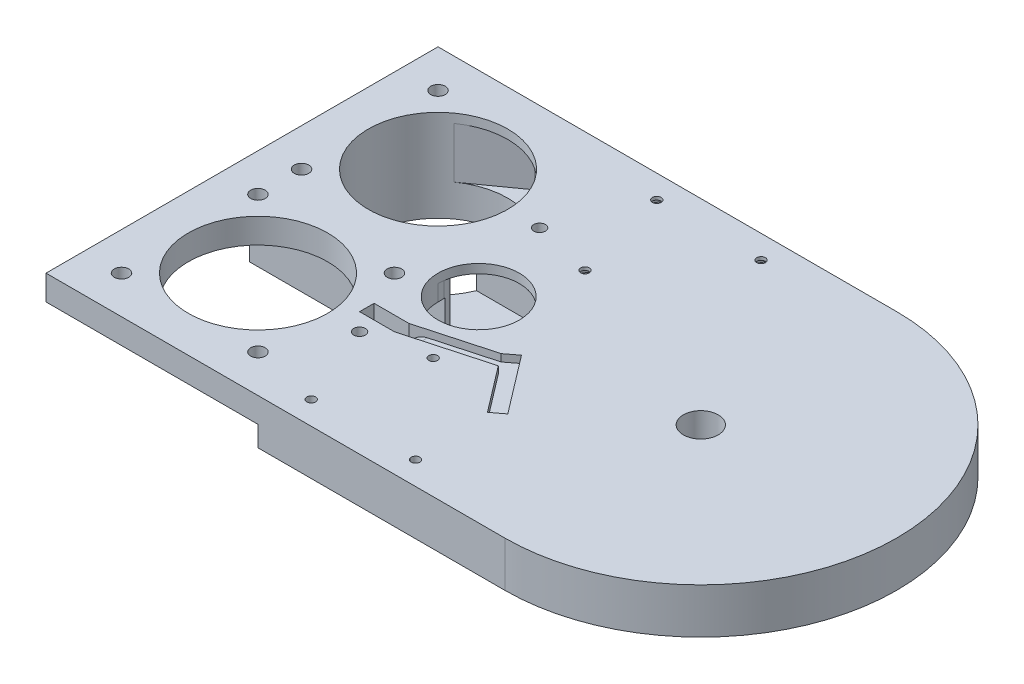
SolidWorks part; units mm, degrees
ref_plane "Alzado" through (0, 0, 0) normal (0, 0, 1) x (1, 0, 0)
ref_plane "Planta" through (0, 0, 0) normal (0, 1, 0) x (1, 0, 0)
ref_plane "Vista lateral" through (0, 0, 0) normal (1, 0, 0) x (0, 0, -1)
sketch "Croquis1" plane through (0, 0, 0) normal (0, 1, 0) x (1, 0, 0)
  line L1 (0, -67.5) -> (-158, -67.5)
  line L3 (0, 67.5) -> (-158, 67.5)
  line L4 (-158, -67.5) -> (-158, 67.5)
  arc A0 (0, -67.5) -> (0, 67.5) centre (0, 0) ccw
  dimension "D2" = 135
  dimension "D1" = 158
extrude "Saliente-Extruir4" add sketch "Croquis1" along normal blind 8.6
sketch "Croquis3" plane through (0, 0, 0) normal (0, -1, 0) x (1, 0, 0)
  line L0 (-85, -67.5) -> (-68.1481, -2.5)
  line L1 (-71.4961, -15.4136) -> (-68.1506, -2.5096) construction
  line L3 (-68.1481, -2.5) -> (-158, -2.5)
  line L4 (-158, -2.5) -> (-158, -67.5)
  line L5 (-158, -67.5) -> (-85, -67.5)
extrude "Saliente-Extruir2" add sketch "Croquis3" along normal up to surface (23 mm away)
sketch "Croquis2" plane through (0, 0, 0) normal (0, 1, 0) x (1, 0, 0)
  line L0 (-17.38, 0) -> (17.38, 0) construction
  circle A0 centre (-76.5, 0) radius 14
  circle A2 centre (-121.5, 31) radius 24
  circle A3 centre (-121.5, -31) radius 24
  dimension "D1" = 28
  dimension "D2" = 48
extrude "Cortar-Extruir1" cut sketch "Croquis2" along normal through all both and the other way through all
sketch "Croquis5" plane through (0, 8.6, 0) normal (0, 1, 0) x (1, 0, 0)
  circle A0 centre (-145, -7.5) radius 2.5
  circle A1 centre (-145, -54.5) radius 2.5
  circle A2 centre (-98, -54.5) radius 2.5
  circle A3 centre (-98, -7.5) radius 2.5
  circle A4 centre (-145, 7.5) radius 2.5
  circle A5 centre (-145, 54.5) radius 2.5
  dimension "D1" = 5
extrude "Cortar-Extruir2" cut sketch "Croquis5" against normal through all
sketch "Croquis6" plane through (0, 8.6, 0) normal (0, 1, 0) x (1, 0, 0)
  line L0 (0, -67.5) -> (-85, -67.5)
  line L1 (-85, -67.5) -> (-70.8172, -12.7947)
  line L2 (0, 67.5) -> (-85, 67.5)
  line L3 (-85, 67.5) -> (-70.8172, 12.7947)
  line L4 (0, 67.5) -> (-158, 67.5) construction
  arc A1 (0, -67.5) -> (0, 67.5) centre (0, 0) ccw
  arc A3 (-70.8172, -12.7947) -> (-70.8172, 12.7947) centre (-76.5, 0) ccw
  circle A4 centre (-76.5, 0) radius 14 construction
  arc A5 (0, -67.5) -> (0, 67.5) centre (0, 0) ccw construction
extrude "Saliente-Extruir3" add sketch "Croquis6" against normal blind 15.6
sketch "Croquis7" plane through (0, 0, 0) normal (0, 1, 0) x (1, 0, 0)
  circle A0 centre (0, 0) radius 6
  dimension "D1" = 12
extrude "Cortar-Extruir3" cut sketch "Croquis7" against normal through all both and the other way through all
sketch "Croquis8" plane through (0, -7, 0) normal (0, -1, 0) x (1, 0, 0)
  line L0 (0, -63) -> (-116.397, -63)
  line L1 (-119.3042, -62.068) -> (-135.4544, -50.5263)
  line L2 (-158, -67.5) -> (-158, -2.5) construction
  line L3 (-121.5, -7) -> (-95.5, -7)
  line L4 (-90.5, -2) -> (-90.5, 0)
  arc A0 (0, -63) -> (-61.2515, 14.7395) centre (0, 0) ccw
  circle A1 centre (-121.5, -31) radius 24 construction
  arc A2 (-121.5, -7) -> (-135.4544, -50.5263) centre (-121.5, -31) ccw
  arc A4 (-70.8172, 12.7947) -> (-90.275, -2.5) centre (-76.5, 0) ccw construction
  arc A7 (-70.8172, 12.7947) -> (-90.5, 0) centre (-76.5, 0) ccw
  arc A10 (-70.8172, -12.7947) -> (-70.8172, 12.7947) centre (-76.5, 0) ccw construction
  arc A11 (-68.8462, 11.7226) -> (-70.8172, 12.7947) centre (-76.5, 0) ccw
  arc A12 (-61.2515, 14.7395) -> (-68.8462, 11.7226) centre (-66.1127, 15.9093) cw
  arc A13 (-90.5, -2) -> (-95.5, -7) centre (-95.5, -2) cw
  arc A14 (-116.397, -63) -> (-119.3042, -62.068) centre (-116.397, -58) cw
  point P27 (-118, -63)
  dimension "D1" = 126
  dimension "D3" = 5
  dimension "D4" = 5
  dimension "D5" = 5
  dimension "D2" = 40
extrude "Cortar-Extruir4" cut sketch "Croquis8" against normal blind 12.5 and the other way blind 5 body kept at (0, 8.6, 67.5)
fillet "Redondeo1" radius 2 1 edges at (-70.8172, -17.5, -12.7947)
sketch "Croquis9" plane through (0, 5.5, 0) normal (0, -1, 0) x (1, 0, 0)
  circle A0 centre (0, 0) radius 6 construction
  circle A1 centre (0, 0) radius 6
  circle A2 centre (0, 0) radius 16.85
  dimension "D1" = 33.7
extrude "Saliente-Extruir5" add sketch "Croquis9" along normal blind 4.65
sketch "Croquis10" plane through (0, 0.85, 0) normal (0, -1, 0) x (1, 0, 0)
  circle A0 centre (0, 0) radius 6 construction
  circle A1 centre (0, 0) radius 6
  circle A2 centre (0, 0) radius 10
  dimension "D1" = 20
extrude "Saliente-Extruir6" add sketch "Croquis10" along normal blind 29
fillet "Redondeo2" radius 0.5 1 edges at (0, 0.85, -16.85)
fillet "Redondeo3" radius 2 1 edges at (0, 5.5, -16.85)
sketch "Croquis11" plane through (0, 5.5, 0) normal (0, -1, 0) x (1, 0, 0)
  line L0 (-121.5, -31) -> (-75.537, -31) construction
  line L1 (-71.7118, -16.2457) -> (-85, -67.5) construction
  line L2 (-73.2037, -22) -> (-77.8704, -40)
  line L3 (-99.2514, -22) -> (-73.2037, -22)
  line L4 (-99.2514, -40) -> (-77.8704, -40)
  circle A0 centre (-121.5, -31) radius 24 construction
  arc A1 (-99.2514, -40) -> (-99.2514, -22) centre (-121.5, -31) ccw
  dimension "D1" = 9
extrude "Saliente-Extruir7" add sketch "Croquis11" along normal up to next
sketch "Croquis12" plane through (0, -7, 0) normal (0, -1, 0) x (1, 0, 0)
  line L2 (-63.0732, 14.8024) -> (-77.256, 69.5077)
  line L3 (-63.0732, 14.8024) -> (-77.256, 69.5077) construction
  line L4 (20.2125, 0) -> (-20.2125, 0) construction
  line L5 (-85, 59.5) -> (0, 59.5)
  line L6 (-85, 59.5) -> (0, 59.5) construction
  circle A0 centre (0, 0) radius 71 construction
  circle A2 centre (-74.6614, 59.5) radius 1.5
  circle A3 centre (-66.0127, 26.1405) radius 1.5
  circle A4 centre (-38.7395, 59.5) radius 1.5
  circle A5 centre (-38.7395, -59.5) radius 1.5
  circle A6 centre (-74.6614, -59.5) radius 1.5
  circle A7 centre (-66.0127, -26.1405) radius 1.5
  circle A8 centre (0, 0) radius 67.5 construction
  arc A9 (0, -67.5) -> (0, 67.5) centre (0, 0) ccw construction
  dimension "D1" = 142
  dimension "D4" = 3
  dimension "D2" = 8
  dimension "D3" = 8
extrude "Cortar-Extruir5" cut sketch "Croquis12" against normal through all
sketch "Croquis13" plane through (0, 5.5, 0) normal (0, -1, 0) x (1, 0, 0)
  line L1 (-70.9087, -59.5) -> (-72.785, -56.25)
  line L2 (-72.785, -56.25) -> (-76.5378, -56.25)
  line L3 (-76.5378, -56.25) -> (-78.4142, -59.5)
  line L4 (-78.4142, -59.5) -> (-76.5378, -62.75)
  line L5 (-76.5378, -62.75) -> (-72.785, -62.75)
  line L6 (-72.785, -62.75) -> (-70.9087, -59.5)
  line L7 (-62.2599, -26.1405) -> (-64.1363, -22.8905)
  line L8 (-64.1363, -22.8905) -> (-67.8891, -22.8905)
  line L9 (-67.8891, -22.8905) -> (-69.7655, -26.1405)
  line L10 (-69.7655, -26.1405) -> (-67.8891, -29.3905)
  line L11 (-67.8891, -29.3905) -> (-64.1363, -29.3905)
  line L12 (-64.1363, -29.3905) -> (-62.2599, -26.1405)
  line L13 (-34.9867, -59.5) -> (-36.8631, -56.25)
  line L14 (-36.8631, -56.25) -> (-40.6159, -56.25)
  line L15 (-40.6159, -56.25) -> (-42.4923, -59.5)
  line L16 (-42.4923, -59.5) -> (-40.6159, -62.75)
  line L17 (-40.6159, -62.75) -> (-36.8631, -62.75)
  line L18 (-36.8631, -62.75) -> (-34.9867, -59.5)
  circle A0 centre (-74.6614, -59.5) radius 3.25 construction
  circle A1 centre (-66.0127, -26.1405) radius 3.25 construction
  circle A2 centre (-38.7395, -59.5) radius 3.25 construction
  dimension "D1" = 6.5
extrude "Cortar-Extruir6" cut sketch "Croquis13" against normal blind 2
sketch "Croquis14" plane through (0, -7, 0) normal (0, -1, 0) x (1, 0, 0)
  circle A0 centre (-66.0127, 26.1405) radius 3
  circle A1 centre (-74.6614, 59.5) radius 3
  circle A2 centre (-38.7395, 59.5) radius 3
  dimension "D1" = 6
extrude "Cortar-Extruir7" cut sketch "Croquis14" against normal blind 3.7
sketch "Croquis15" plane through (0, -23, 0) normal (0, -1, 0) x (1, 0, 0)
  line L0 (-71.7118, -16.2457) -> (-85, -67.5) construction
  line L1 (-97.5, -31) -> (-75.537, -31) construction
  line L2 (20.2125, 0) -> (-20.2125, 0) construction
  circle A0 centre (-121.5, -31) radius 24 construction
  circle A1 centre (-86.5185, -31) radius 2
  circle A2 centre (-86.5185, 31) radius 2
  dimension "D1" = 4
extrude "Cortar-Extruir8" cut sketch "Croquis15" against normal through all
sketch "Croquis16" plane through (0, 0, 0) normal (0, -1, 0) x (1, 0, 0)
  circle A0 centre (-86.5185, 31) radius 4
  dimension "D1" = 8
extrude "Cortar-Extruir9" cut sketch "Croquis16" against normal blind 4
sketch "Croquis17" plane through (0, -23, 0) normal (0, -1, 0) x (1, 0, 0)
  line L1 (-82.1884, -31) -> (-84.3535, -27.25)
  line L2 (-84.3535, -27.25) -> (-88.6836, -27.25)
  line L3 (-88.6836, -27.25) -> (-90.8486, -31)
  line L4 (-90.8486, -31) -> (-88.6836, -34.75)
  line L5 (-88.6836, -34.75) -> (-84.3535, -34.75)
  line L6 (-84.3535, -34.75) -> (-82.1884, -31)
  circle A0 centre (-86.5185, -31) radius 3.75 construction
  dimension "D1" = 7.5
extrude "Cortar-Extruir10" cut sketch "Croquis17" against normal blind 10
sketch "Croquis19" plane through (0, 8.6, 0) normal (0, 1, 0) x (1, 0, 0)
  line L0 (0, -20.2125) -> (0, 20.2125) construction
  line L1 (-158, -67.5) -> (0, -67.5) construction
  line L2 (-52.483, -17.2558) -> (-40.4717, -33.0039)
  line L3 (-55.6329, -13.1259) -> (-51.6573, -10.0936)
  line L4 (-40.4717, -33.0039) -> (-36.4961, -29.9717)
  line L5 (-51.6573, -10.0936) -> (-36.4961, -29.9717)
  line L6 (-55.6329, -13.1259) -> (-36.4961, -29.9717) construction
  line L7 (-40.4717, -33.0039) -> (-51.6573, -10.0936) construction
  line L8 (-40, -29.5) -> (-62.5, 0) construction
  line L9 (-20.2125, 0) -> (20.2125, 0) construction
  line L10 (-80.5185, -20) -> (-55.6329, -13.1259)
  line L11 (-92.5185, -25) -> (-80.5185, -25)
  line L12 (-92.5185, -25) -> (-92.5185, -20)
  line L13 (-92.5185, -20) -> (-80.5185, -20)
  line L15 (-92.5185, -25) -> (-80.5185, -20) construction
  line L16 (-92.5185, -20) -> (-80.5185, -25) construction
  line L17 (-80.5185, -25) -> (-52.483, -17.2558)
  circle A0 centre (-40, -29.5) radius 2.5 construction
  circle A1 centre (-76.5, 0) radius 14 construction
  circle A2 centre (-86.5185, -31) radius 2 construction
  circle A3 centre (-86.5185, -31) radius 2 construction
  point P7 (-46.0645, -21.5488)
  point P19 (-86.5185, -22.5)
  dimension "D1" = 5
  dimension "D2" = 40
  dimension "D3" = 38
  dimension "D4" = 25
  dimension "D5" = 5
  dimension "D6" = 12
  dimension "D7" = 6
extrude "Cortar-Extruir11" cut sketch "Croquis19" against normal blind 2.5
sketch "Croquis20" plane through (0, 8.6, 0) normal (0, 1, 0) x (1, 0, 0)
  line L0 (-80.5185, -20) -> (-92.5185, -20) construction
  line L1 (-92.5185, -25) -> (-80.5185, -25)
  line L2 (-92.5185, -25) -> (-92.5185, -20)
  line L3 (-92.5185, -20) -> (-80.5185, -20)
  line L4 (-80.5185, -25) -> (-80.5185, -20)
  line L5 (-92.5185, -25) -> (-80.5185, -20) construction
  line L6 (-92.5185, -20) -> (-80.5185, -25) construction
  line L7 (-92.5185, -20) -> (-92.5185, -25) construction
  line L8 (-92.5185, -25) -> (-80.5185, -25) construction
  point P0 (-86.5185, -22.5)
extrude "Cortar-Extruir12" cut sketch "Croquis20" against normal through all
fillet "Redondeo4" radius 5 1 edges at (-80.5185, 6.1, 22.5)
